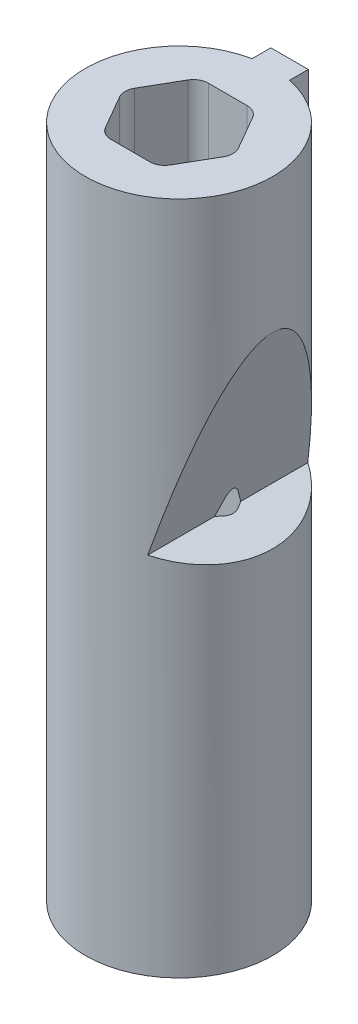
SolidWorks part; units mm, degrees
ref_plane "Front Plane" through (0, 0, 0) normal (0, 0, 1) x (1, 0, 0)
ref_plane "Top Plane" through (0, 0, 0) normal (0, 1, 0) x (1, 0, 0)
ref_plane "Right Plane" through (0, 0, 0) normal (1, 0, 0) x (0, 0, -1)
sketch "Sketch1" plane through (0, 0, 0) normal (0, 1, 0) x (1, 0, 0)
  circle A0 centre (0, 0) radius 2.5
  dimension "D1" = 5
extrude "Boss-Extrude1" add sketch "Sketch1" along normal blind 18
sketch "Sketch3" plane through (0, 18, 0) normal (0, 1, 0) x (1, 0, 0)
  line L0 (-0.5, 2.4495) -> (0.5, 2.4495)
  line L1 (0, 0) -> (0, 2.5) construction
  line L2 (-0.5, 2.4495) -> (-0.5, 2.9495)
  line L3 (-0.5, 2.9495) -> (0.5, 2.9495)
  line L4 (0.5, 2.9495) -> (0.5, 2.4495)
  circle A2 centre (0, 0) radius 2.5 construction
  circle A3 centre (0, 0) radius 2.5 construction
  point P3 (0, 2.4495)
  dimension "D1" = 1
  dimension "D2" = 0.5
extrude "Boss-Extrude2" add sketch "Sketch3" against normal blind 5
sketch "Sketch4" plane through (0, 0, 0) normal (0, -1, 0) x (1, 0, 0)
  line L0 (1.5, 0) -> (-1.5, 0) construction
  line L1 (-0.5191, -1.299) -> (0.5191, -1.299)
  line L2 (0.8655, -1.099) -> (1.3845, -0.2)
  line L3 (1.3845, 0.2) -> (0.8655, 1.099)
  line L4 (0.5191, 1.299) -> (-0.5191, 1.299)
  line L5 (-0.8655, 1.099) -> (-1.3845, 0.2)
  line L6 (-1.3845, -0.2) -> (-0.8655, -1.099)
  circle A1 centre (0, 0) radius 1.299 construction
  arc A2 (0.8655, 1.099) -> (0.5191, 1.299) centre (0.5191, 0.899) ccw
  arc A3 (-0.5191, 1.299) -> (-0.8655, 1.099) centre (-0.5191, 0.899) ccw
  arc A4 (-1.3845, 0.2) -> (-1.3845, -0.2) centre (-1.0381, 0) ccw
  arc A5 (-0.5191, -1.299) -> (-0.8655, -1.099) centre (-0.5191, -0.899) cw
  arc A6 (0.5191, -1.299) -> (0.8655, -1.099) centre (0.5191, -0.899) ccw
  arc A7 (1.3845, -0.2) -> (1.3845, 0.2) centre (1.0381, 0) ccw
  dimension "D1" = 3
  dimension "D2" = 0.4
sketch "Sketch5" plane through (0, 0, 0) normal (0, 0, 1) x (1, 0, 0)
  line L0 (2.5, 0) -> (2.5, 18) construction
  line L1 (2.5, 0) -> (2.5, 18) construction
  line L2 (2.5, 14.4) -> (1.3, 9.7215)
  line L3 (1.3, 9.7215) -> (2.5, 9.4)
  line L4 (2.5, 9.4) -> (2.5, 14.4)
  dimension "D1" = 75
  dimension "D2" = 5
  dimension "D3" = 9.4
  dimension "D4" = 1.2
extrude "Cut-Extrude1" cut sketch "Sketch5" against normal blind 4 and the other way blind 4
extrude "Cut-Extrude2" cut sketch "Sketch4" against normal blind 34
